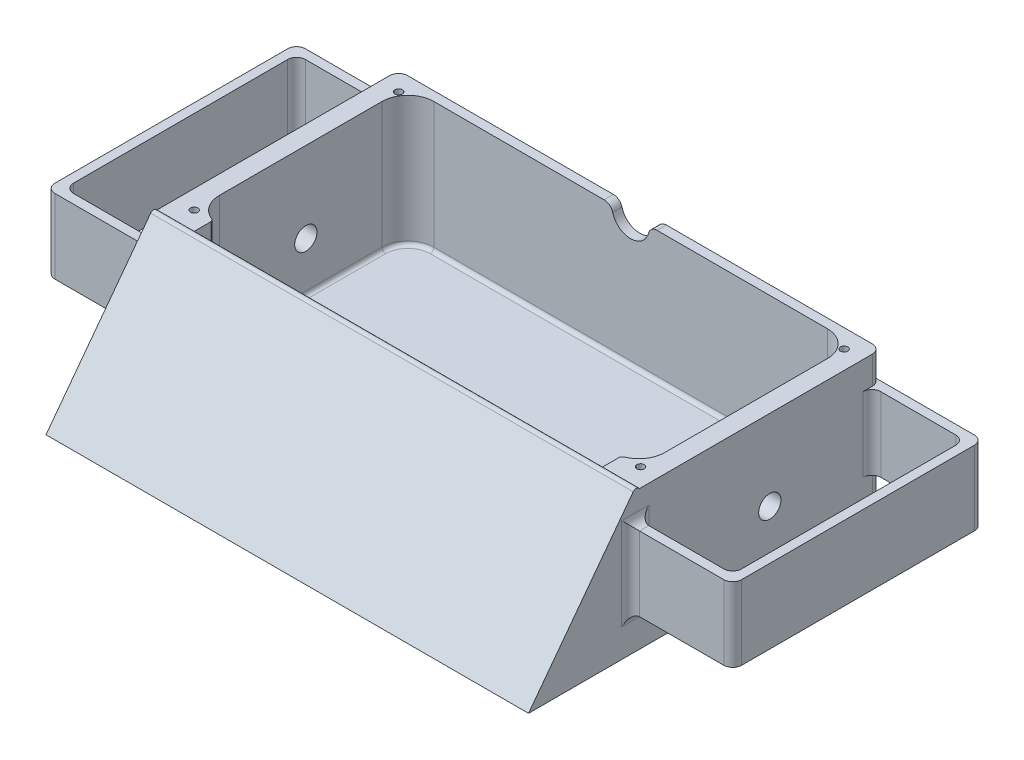
SolidWorks part; units mm, degrees
note: The reader was unsure of these and kept them because the rebuilt part matched: shared geometry of "Sketch1<3>".
ref_plane "Front Plane" through (0, 0, 0) normal (0, 0, 1) x (1, 0, 0)
ref_plane "Top Plane" through (0, 0, 0) normal (0, 1, 0) x (1, 0, 0)
ref_plane "Right Plane" through (0, 0, 0) normal (1, 0, 0) x (0, 0, -1)
other "Bounding Box"
ref_plane "Default Plane" through (-8.9266, -12.7485, 0) normal (-0.1736, 0.9848, 0) x (0.9848, 0.1736, 0)
sketch "Sketch1" plane through (0, 0, 0) normal (0, 1, 0) x (1, 0, 0)
  line L0 (0, 0) -> (0, 38.1) construction
  line L1 (76.2, 38.1) -> (-76.2, 38.1)
  line L2 (76.2, 38.1) -> (76.2, -38.1)
  line L3 (76.2, -38.1) -> (-76.2, -38.1)
  line L4 (-76.2, 38.1) -> (-76.2, -38.1)
  line L5 (76.2, 38.1) -> (-76.2, -38.1) construction
  line L6 (76.2, -38.1) -> (-76.2, 38.1) construction
  line L7 (-79.375, 41.275) -> (79.375, 41.275)
  line L8 (-79.375, 41.275) -> (-79.375, -41.275)
  line L9 (-79.375, -41.275) -> (79.375, -41.275)
  line L10 (79.375, 41.275) -> (79.375, -41.275)
  line L11 (-79.375, 41.275) -> (79.375, -41.275) construction
  line L12 (-79.375, -41.275) -> (79.375, 41.275) construction
  line L13 (-79.375, 41.275) -> (-117.475, 41.275)
  line L14 (-79.375, 41.275) -> (-79.375, -41.275)
  line L15 (-79.375, -41.275) -> (-117.475, -41.275)
  line L16 (-117.475, 41.275) -> (-117.475, -41.275)
  line L17 (-114.3, 38.1) -> (-82.55, 38.1)
  line L18 (-114.3, 38.1) -> (-114.3, -41.275)
  line L19 (-114.3, -41.275) -> (-82.55, -41.275)
  line L20 (-82.55, 38.1) -> (-82.55, -41.275)
  line L21 (79.375, -41.275) -> (117.475, -41.275)
  line L22 (117.475, 41.275) -> (117.475, -41.275)
  line L23 (79.375, 41.275) -> (117.475, 41.275)
  line L24 (79.375, 41.275) -> (79.375, -41.275)
  line L25 (114.3, -41.275) -> (82.55, -41.275)
  line L26 (82.55, 38.1) -> (82.55, -41.275)
  line L27 (114.3, 38.1) -> (82.55, 38.1)
  line L28 (114.3, 38.1) -> (114.3, -41.275)
  point P0 (0, 0)
  point P6 (0, 0)
  dimension "D1" = 152.4
  dimension "D2" = 76.2
  dimension "D3" = 3.175
  dimension "D4" = 3.175
  dimension "D5" = 38.1
  dimension "D6" = 3.175
  dimension "D7" = 3.175
  dimension "D8" = 6.35
extrude "Boss-Extrude1" add sketch "Sketch1" along normal blind 50.8 contours L10 L7 L8 L9 L4 L1 L2 L3 | L27 L28 L21 L22 L23 L10 L26 | L13 L16 L15 L14 | L17 L20 L19 L18
extrude "Boss-Extrude2" add sketch "Sketch1<3>" along normal blind 3.175 contours L1 L4 L3 L2
sketch "Sketch1<3>" plane through (0, 0, 0) normal (0, 1, 0) x (1, 0, 0) same geometry as "Sketch1"
sketch "Sketch8" plane through (0, 0, 41.275) normal (0, 0, 1) x (1, 0, 0)
  line L0 (-82.55, 50.8) -> (82.55, 50.8) construction
  line L1 (-76.2, 50.8) -> (76.2, 50.8)
  line L2 (-76.2, 50.8) -> (-76.2, 3.175)
  line L3 (-76.2, 3.175) -> (76.2, 3.175)
  line L4 (76.2, 50.8) -> (76.2, 3.175)
  line L5 (-82.55, 50.8) -> (-82.55, 0) construction
  line L6 (82.55, 50.8) -> (82.55, 0) construction
  line L7 (-82.55, 0) -> (82.55, 0) construction
  dimension "D1" = 6.35
  dimension "D2" = 6.35
  dimension "D3" = 3.175
extrude "Cut-Extrude1" cut sketch "Sketch8" against normal blind 6.35
sketch "Sketch10" plane through (-82.55, 0, 0) normal (-1, 0, 0) x (0, 0, 1)
  line L0 (41.275, 50.8) -> (79.375, 0)
  line L1 (79.375, 0) -> (41.275, 0)
  line L2 (41.275, 45.5083) -> (73.025, 3.175)
  line L3 (41.275, 50.8) -> (41.275, 0) construction
  line L4 (73.025, 3.175) -> (41.275, 3.175)
  line L5 (41.275, 45.5083) -> (41.275, 50.8)
  line L6 (41.275, 3.175) -> (41.275, 0)
  dimension "D1" = 63.5
  dimension "D2" = 3.175
  dimension "D3" = 3.175
extrude "Boss-Extrude10" add sketch "Sketch10" against normal up to surface (165.1 mm away) up to face at (82.55, 25.4, 1.5875)
sketch "Sketch11" plane through (82.55, 0, 0) normal (1, 0, 0) x (0, 0, -1)
  line L0 (-41.275, 45.5083) -> (-73.025, 3.175)
  line L1 (-73.025, 3.175) -> (-41.275, 3.175)
  line L2 (-41.275, 3.175) -> (-41.275, 45.5083)
extrude "Boss-Extrude11" add sketch "Sketch11" against normal blind 3.175
sketch "Sketch12" plane through (0, 0, 41.275) normal (0, 0, 1) x (1, 0, 0)
  line L0 (82.55, 50.8) -> (82.55, 0) construction
  line L1 (117.475, 0) -> (82.55, 0)
  line L2 (117.475, 0) -> (117.475, 38.1)
  line L3 (117.475, 38.1) -> (82.55, 38.1)
  line L4 (82.55, 0) -> (82.55, 38.1)
  dimension "D1" = 38.1
extrude "Boss-Extrude12" add sketch "Sketch12" along normal blind 3.175
mirror "Mirror2" about plane through (0, 0, 0) normal (1, 0, 0) of "Boss-Extrude11"
mirror "Mirror3" about plane through (0, 0, 0) normal (1, 0, 0) of "Boss-Extrude12"
sketch "Sketch13" plane through (0, 0, 41.275) normal (0, 0, 1) x (1, 0, 0)
  line L1 (117.475, 38.1) -> (82.55, 38.1)
  line L2 (117.475, 38.1) -> (117.475, 50.8)
  line L3 (117.475, 50.8) -> (82.55, 50.8)
  line L4 (82.55, 38.1) -> (82.55, 50.8)
  line L5 (-117.475, 50.8) -> (-82.55, 50.8)
  line L6 (-117.475, 50.8) -> (-117.475, 38.1)
  line L7 (-117.475, 38.1) -> (-82.55, 38.1)
  line L9 (-82.55, 38.1) -> (-82.55, 50.8)
  dimension "D1" = 12.7
extrude "Cut-Extrude2" cut sketch "Sketch13" against normal through all both and the other way through all
sketch "Sketch14" plane through (0, 0, 0) normal (0, -1, 0) x (-1, 0, 0)
  line L1 (-82.55, -44.45) -> (-117.475, -44.45)
  line L2 (-82.55, -44.45) -> (-82.55, 41.275)
  line L3 (-82.55, 41.275) -> (-117.475, 41.275)
  line L4 (-117.475, -44.45) -> (-117.475, 41.275)
extrude "Cut-Extrude3" cut sketch "Sketch14" against normal blind 12.7
mirror "Mirror4" about plane through (0, 0, 0) normal (1, 0, 0) of "Cut-Extrude3"
sketch "Sketch16" plane through (-82.55, 0, 0) normal (-1, 0, 0) x (0, 0, 1)
  line L0 (-41.275, 0) -> (79.375, 0) construction
  line L1 (-41.275, 38.1) -> (-41.275, 12.7) construction
  circle A0 centre (-3.175, 20.066) radius 3.81
  dimension "D1" = 7.62
  dimension "D3" = 38.1
  dimension "D2" = 20.066
extrude "Cut-Extrude4" cut sketch "Sketch16" against normal blind 173.99 and the other way blind 6.096
sketch "Sketch17" plane through (0, 50.8, 0) normal (0, 1, 0) x (1, 0, 0)
  line L1 (-82.55, 41.275) -> (82.55, 41.275)
  line L2 (-82.55, 41.275) -> (-82.55, -41.275)
  line L3 (-82.55, -41.275) -> (82.55, -41.275)
  line L4 (82.55, 41.275) -> (82.55, -41.275)
extrude "Cut-Extrude5" cut sketch "Sketch17" against normal blind 3.175
sketch "Sketch20" plane through (0, 0, 0) normal (0, -1, 0) x (-1, 0, 0)
  line L1 (82.55, -41.275) -> (-82.55, -41.275)
  line L2 (82.55, -41.275) -> (82.55, 41.275)
  line L3 (82.55, 41.275) -> (-82.55, 41.275)
  line L4 (-82.55, -41.275) -> (-82.55, 41.275)
sketch "Sketch25" plane through (0, 3.175, 0) normal (0, 1, 0) x (1, 0, 0)
  line L1 (76.2, -41.275) -> (69.85, -41.275)
  line L2 (76.2, -41.275) -> (76.2, -34.925)
  line L3 (76.2, -34.925) -> (69.85, -34.925)
  line L4 (69.85, -41.275) -> (69.85, -34.925)
  line L5 (-76.2, -41.275) -> (-69.85, -41.275)
  line L6 (-76.2, -41.275) -> (-76.2, -34.925)
  line L7 (-76.2, -34.925) -> (-69.85, -34.925)
  line L8 (-69.85, -41.275) -> (-69.85, -34.925)
  dimension "D1" = 6.35
  dimension "D2" = 6.35
  dimension "D3" = 6.35
  dimension "D4" = 6.35
extrude "Boss-Extrude16" add sketch "Sketch25" along normal up to surface (44.45 mm away)
fillet "Fillet2" radius 8.89 4 edges at (76.2, 25.4, 34.925) (76.2, 25.4, -38.1) (-76.2, 25.4, -38.1) (-76.2, 25.4, 34.925)
fillet "Fillet3" radius 1.27 17 edges at (74.6125, 3.175, 41.275) (79.375, 3.175, 57.15) (0, 3.175, 73.025) (-79.375, 3.175, 57.15) (-74.6125, 3.175, 41.275) (-69.85, 3.175, 38.1) (-74.4379, 3.175, 31.7184) (-76.2, 3.175, -1.4022) (-73.5962, 3.175, -35.4962) (0, 3.175, -38.1) (73.5962, 3.175, -35.4962) (76.2, 3.175, -1.4022) (74.4379, 3.175, 31.7184) (69.85, 3.175, 38.1) (-69.85, 25.4, 34.925) (69.85, 25.4, 34.925) (0, 50.8, 41.275)
sketch "Sketch26" plane through (0, 47.625, 0) normal (0, 1, 0) x (1, 0, 0)
  line L0 (82.55, 41.275) -> (-82.55, 41.275) construction
  line L2 (-82.55, 41.275) -> (-82.55, -41.4451) construction
  line L3 (0, 0) -> (0, 41.275) construction
  line L4 (0, 0) -> (-82.55, -0.0851) construction
  circle A1 centre (-76.2, 34.925) radius 1.27
  circle A2 centre (76.2, 34.925) radius 1.27
  circle A3 centre (76.2718, -34.7679) radius 1.27
  circle A4 centre (-76.1279, -35.082) radius 1.27
  point P6 (0, 0)
  point P10 (0, 41.275)
  dimension "D1" = 2.54
  dimension "D2" = 6.35
  dimension "D3" = 6.35
extrude "Cut-Extrude8" cut sketch "Sketch26" against normal through all both and the other way through all
fillet "Fillet4" radius 3.048 22 edges at (-114.3, 25.4, 41.275) (-114.3, 25.4, -38.1) (-82.55, 25.4, -38.1) (-82.55, 25.4, 41.275) (82.55, 25.4, 41.275) (114.3, 25.4, 41.275) (114.3, 25.4, -38.1) (82.55, 25.4, -38.1) (82.55, 12.7, 42.8625) (-82.55, 12.7, 42.8625) (-82.55, 38.1, 42.8625) (82.55, 38.1, 42.8625) (117.475, 25.4, -41.275) (117.475, 25.4, 44.45) (82.55, 25.4, 44.45) (-117.475, 25.4, 44.45) (-82.55, 25.4, 44.45) (-117.475, 25.4, -41.275) (-82.55, 6.35, -41.275) (82.55, 6.35, -41.275) (82.55, 42.8625, -41.275) (-82.55, 42.8625, -41.275)
sketch "Sketch27" plane through (0, 0, -41.275) normal (0, 0, -1) x (-1, 0, 0)
  line L0 (69.85, 46.99) -> (-69.85, 46.99) construction
  circle A0 centre (0, 46.99) radius 6.35
  dimension "D1" = 12.7
extrude "Cut-Extrude9" cut sketch "Sketch27" against normal blind 7.366 and the other way through all
fillet "Fillet5" radius 3.048 1 edges at (-6.3182, 47.625, -39.6875)
